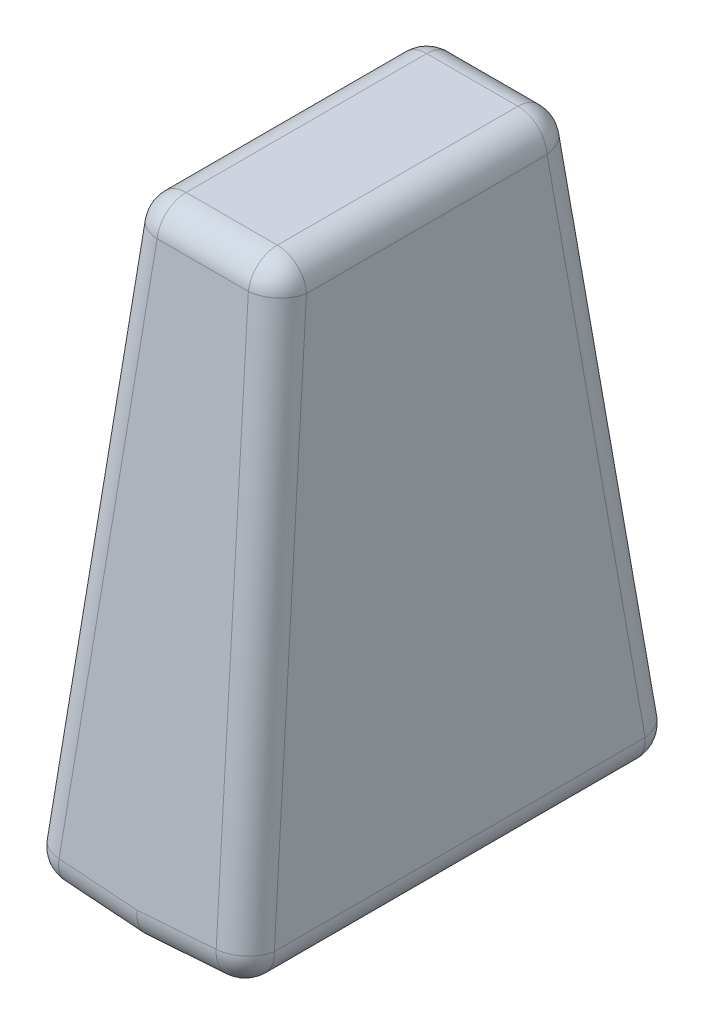
SolidWorks part; units mm, degrees
ref_plane "Płaszczyzna przednia" through (0, 0, 0) normal (0, 0, 1) x (1, 0, 0)
ref_plane "Płaszczyzna górna" through (0, 0, 0) normal (0, 1, 0) x (1, 0, 0)
ref_plane "Płaszczyzna prawa" through (0, 0, 0) normal (1, 0, 0) x (0, 0, -1)
sketch "Szkic1" plane through (0, 0, 0) normal (0, 0, 1) x (1, 0, 0)
  line L0 (0, 0) -> (0, 40)
  line L1 (3.1225, 40) -> (-3.1225, 40)
  line L2 (-5.1185, 38.1262) -> (-7.3738, 2.4704)
  line L3 (-5.504, 0.3481) -> (0, 0)
  line L4 (5.504, 0.3481) -> (0, 0)
  line L5 (5.1185, 38.1262) -> (7.3738, 2.4704)
  arc A0 (-3.1225, 40) -> (-5.1185, 38.1262) centre (-3.1225, 38) ccw
  arc A1 (-7.3738, 2.4704) -> (-5.504, 0.3481) centre (-5.3777, 2.3441) ccw
  arc A2 (7.3738, 2.4704) -> (5.504, 0.3481) centre (5.3777, 2.3441) cw
  arc A3 (3.1225, 40) -> (5.1185, 38.1262) centre (3.1225, 38) cw
  point P7 (-5, 40)
  point P10 (-7.5, 0.4744)
  point P17 (7.5, 0.4744)
  point P18 (5, 40)
  dimension "D5" = 2
  dimension "D1" = 40
  dimension "D2" = 90
  dimension "D3" = 5
  dimension "D4" = 7.5
extrude "Dodanie-wyciągnięcie1" add sketch "Szkic1" along normal blind 30 contours L2 A1 L3 L0 L1 A0 | A3 L1 L0 L4 A2 L5 region at (-3.1441, 18.7866, 0) region at (3.1441, 18.7866, 0)
ref_plane "Płaszczyzna1" through (5.1225, 0, 0) normal (1, 0, 0) x (0, 0, -1)
ref_plane "Płaszczyzna2" through (15.1225, 0, 0) normal (1, 0, 0) x (0, 0, -1)
sketch "Szkic7" plane through (15.1225, 0, 0) normal (1, 0, 0) x (0, 0, -1)
  line L0 (-25, 40) -> (-5, 40)
  line L1 (-30, 40) -> (0, 40) construction
  line L2 (-5, 40) -> (0, 0)
  line L3 (0, 0) -> (-30, 0)
  line L4 (-30, 0) -> (0, 0) construction
  line L5 (-15, 0) -> (-15, 40)
  line L6 (-25, 40) -> (-30, 0)
  line L8 (0, 0) -> (-30, 0)
  line L9 (0, 0) -> (0, 40)
  line L10 (0, 40) -> (-30, 40)
  line L11 (-30, 0) -> (-30, 40)
  dimension "D1" = 10
  dimension "D2" = 15
  dimension "D3" = 40
extrude "Wytnij-wyciągnięcie11" cut sketch "Szkic7" against normal through all and the other way through all contours L11 L6 L10 | L9 L10 L2 region at (15.1225, 26.6667, 28.3333) region at (15.1225, 26.6667, 1.6667)
fillet "Zaokrąglenie2" radius 2 18 edges at (0, 40, 5) (-4.4914, 39.4582, 4.9323) (-6.2461, 20.2983, 2.5373) (-6.8784, 1.022, 0.1278) (-2.752, 0.1741, 0.0218) (2.752, 0.1741, 0.0218) (6.8784, 1.022, 0.1278) (6.2461, 20.2983, 2.5373) (4.4914, 39.4582, 4.9323) (4.4914, 39.4582, 25.0677) (6.2461, 20.2983, 27.4627) (6.8784, 1.022, 29.8722) (2.752, 0.1741, 29.9782) (-2.752, 0.1741, 29.9782) (-6.8784, 1.022, 29.8722) (-6.2461, 20.2983, 27.4627) (-4.4914, 39.4582, 25.0677) (0, 40, 25)
